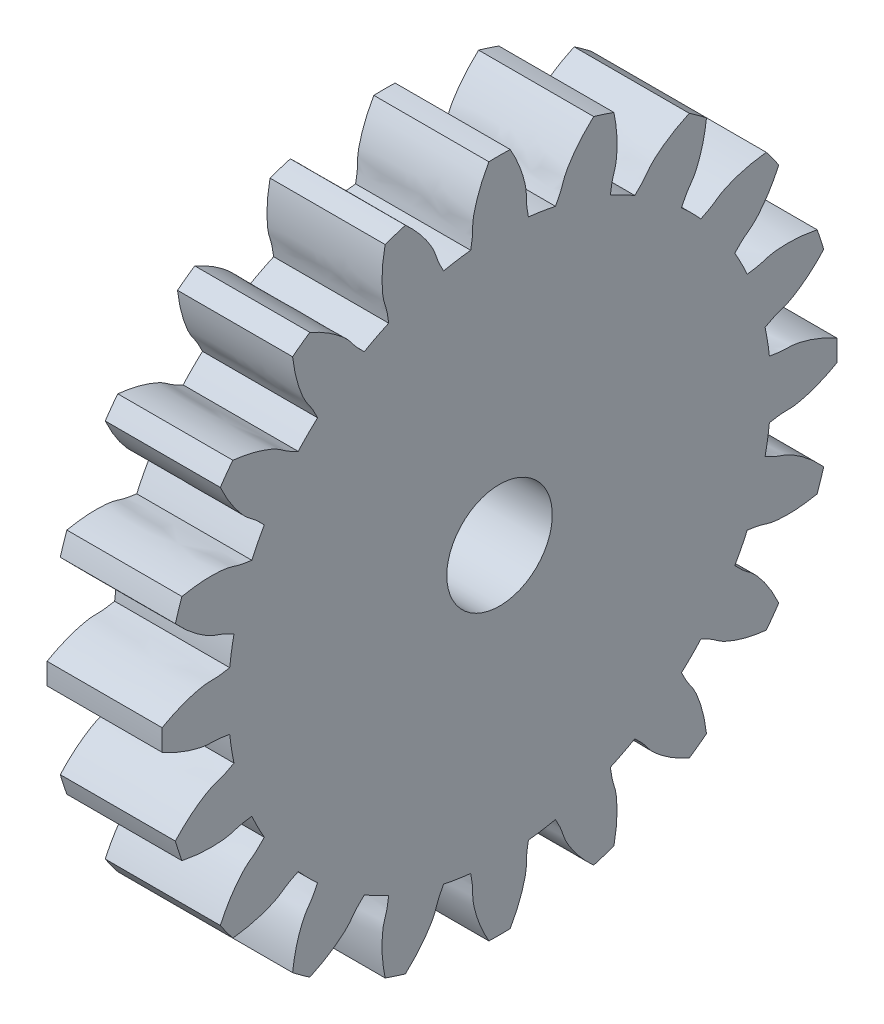
SolidWorks part; units mm, degrees
ref_plane "Front Plane" through (0, 0, 0) normal (0, 0, 1) x (1, 0, 0)
ref_plane "Top Plane" through (0, 0, 0) normal (0, 1, 0) x (1, 0, 0)
ref_plane "Right Plane" through (0, 0, 0) normal (1, 0, 0) x (0, 0, -1)
ref_plane "Plane1" through (0, 2.008, 0) normal (0, -1, 0) x (-1, 0, 0)
ref_plane "Plane2" through (0, 4.8333, 0) normal (0, 1, 0) x (1, 0, 0)
sketch "Sketch41" plane through (0, 0, 0) normal (0, 0, 1) x (1, 0, 0)
  line L0 (-1.5, 8.8) -> (-1.5, 0)
  line L1 (-1.5, 0) -> (1.5, 0)
  line L2 (1.5, 0) -> (1.5, 8.8)
  line L3 (1.5, 8.8) -> (-1.5, 8.8)
  line L4 (-1.5, 0) -> (1.5, 0) construction
revolve "Revolve3" add sketch "Sketch41" angle 360 about L1 reverse direction yes
ref_plane "Plane3" through (-1.5, 0, 0) normal (-1, 0, 0) x (0, 0, 1)
sketch "Sketch47" plane through (-1.5, 0, 0) normal (-1, 0, 0) x (0, 0, 1)
  arc A0 (0.7524, 7.0343) -> (1.4582, 6.9225) centre (0, 0) cw
  arc A1 (2.4537, 8.451) -> (0.2779, 8.7956) centre (0, 0) ccw
  spline S0 degree 3 poles (0.2779, 8.7956) (0.3159, 8.7284) (0.3523, 8.6603) (0.3868, 8.5913) (0.4678, 8.4292) (0.5382, 8.261) (0.5931, 8.0882) (0.6482, 7.9149) (0.6968, 7.7352) (0.7008, 7.5535) (0.7028, 7.4585) (0.7002, 7.3628) (0.7143, 7.2689) (0.7261, 7.1905) (0.7397, 7.1125) (0.7524, 7.0343) knots -0.000231 -0.000231 -0.000231 -0.000231 0 0 0 0.000544 0.000544 0.000544 0.001091 0.001091 0.001091 0.001372 0.001372 0.001372 0.001605 0.001605 0.001605 0.001605
  spline S1 degree 3 poles (1.4582, 6.9225) (1.4944, 6.9929) (1.5314, 7.063) (1.5669, 7.1338) (1.6364, 7.2729) (1.6675, 7.4295) (1.7404, 7.5668) (1.8106, 7.6992) (1.8949, 7.8242) (1.9854, 7.9436) (2.0779, 8.0657) (2.1795, 8.1812) (2.287, 8.2903) (2.3412, 8.3453) (2.3968, 8.3988) (2.4537, 8.451) knots -0.000237 -0.000237 -0.000237 -0.000237 0 0 0 0.000466 0.000466 0.000466 0.000915 0.000915 0.000915 0.001374 0.001374 0.001374 0.001605 0.001605 0.001605 0.001605
extrude "Cut-Extrude22" cut sketch "Sketch47" against normal through all
sketch "Sketch54" plane through (-1.5, 0, 0) normal (-1, 0, 0) x (0, 0, 1)
  arc A0 (2.8893, 6.4575) -> (3.526, 6.1331) centre (0, 0) cw
  arc A1 (4.9451, 7.2791) -> (2.9823, 8.2792) centre (0, 0) ccw
  spline S0 degree 3 poles (2.9823, 8.2792) (2.9976, 8.2036) (3.0112, 8.1276) (3.0227, 8.0513) (3.0497, 7.8721) (3.0646, 7.6903) (3.0635, 7.5091) (3.0623, 7.3272) (3.053, 7.1413) (3.0006, 6.9672) (2.9733, 6.8763) (2.9411, 6.7861) (2.9255, 6.6924) (2.9125, 6.6142) (2.9013, 6.5358) (2.8893, 6.4575) knots -0.000231 -0.000231 -0.000231 -0.000231 0 0 0 0.000544 0.000544 0.000544 0.001091 0.001091 0.001091 0.001372 0.001372 0.001372 0.001605 0.001605 0.001605 0.001605
  spline S1 degree 3 poles (3.526, 6.1331) (3.5822, 6.1889) (3.6391, 6.244) (3.6946, 6.3005) (3.8037, 6.4113) (3.8817, 6.5506) (3.9935, 6.6587) (4.1011, 6.7629) (4.22, 6.8557) (4.3429, 6.9413) (4.4686, 7.0288) (4.601, 7.1073) (4.7369, 7.1779) (4.8054, 7.2134) (4.8749, 7.2471) (4.9451, 7.2791) knots -0.000237 -0.000237 -0.000237 -0.000237 0 0 0 0.000466 0.000466 0.000466 0.000915 0.000915 0.000915 0.001374 0.001374 0.001374 0.001605 0.001605 0.001605 0.001605
extrude "Cut-Extrude23" cut sketch "Sketch54" against normal through all
sketch "Sketch61" plane through (-1.5, 0, 0) normal (-1, 0, 0) x (0, 0, 1)
  arc A0 (4.7433, 5.2486) -> (5.2486, 4.7433) centre (0, 0) cw
  arc A1 (6.9524, 5.3948) -> (5.3948, 6.9524) centre (0, 0) ccw
  spline S0 degree 3 poles (5.3948, 6.9524) (5.386, 6.8758) (5.3754, 6.7993) (5.3628, 6.7232) (5.3331, 6.5444) (5.2911, 6.3669) (5.234, 6.1949) (5.1767, 6.0223) (5.1104, 5.8484) (5.0068, 5.699) (4.9526, 5.6209) (4.8942, 5.5451) (4.8504, 5.4608) (4.8139, 5.3905) (4.779, 5.3194) (4.7433, 5.2486) knots -0.000231 -0.000231 -0.000231 -0.000231 0 0 0 0.000544 0.000544 0.000544 0.001091 0.001091 0.001091 0.001372 0.001372 0.001372 0.001605 0.001605 0.001605 0.001605
  spline S1 degree 3 poles (5.2486, 4.7433) (5.3194, 4.779) (5.3905, 4.8139) (5.4608, 4.8504) (5.5988, 4.9221) (5.716, 5.0305) (5.8557, 5.0987) (5.9903, 5.1645) (6.132, 5.2161) (6.2754, 5.2595) (6.422, 5.304) (6.572, 5.3376) (6.7232, 5.3628) (6.7993, 5.3754) (6.8758, 5.386) (6.9524, 5.3948) knots -0.000237 -0.000237 -0.000237 -0.000237 0 0 0 0.000466 0.000466 0.000466 0.000915 0.000915 0.000915 0.001374 0.001374 0.001374 0.001605 0.001605 0.001605 0.001605
extrude "Cut-Extrude24" cut sketch "Sketch61" against normal through all
sketch "Sketch68" plane through (-1.5, 0, 0) normal (-1, 0, 0) x (0, 0, 1)
  arc A0 (6.1331, 3.526) -> (6.4575, 2.8893) centre (0, 0) cw
  arc A1 (8.2792, 2.9823) -> (7.2791, 4.9451) centre (0, 0) ccw
  spline S0 degree 3 poles (7.2791, 4.9451) (7.2471, 4.8749) (7.2134, 4.8054) (7.1779, 4.7369) (7.0944, 4.5761) (6.9996, 4.4202) (6.8921, 4.2743) (6.7843, 4.1279) (6.6675, 3.9829) (6.5228, 3.8729) (6.4472, 3.8154) (6.3682, 3.7613) (6.3005, 3.6946) (6.244, 3.6391) (6.1889, 3.5822) (6.1331, 3.526) knots -0.000231 -0.000231 -0.000231 -0.000231 0 0 0 0.000544 0.000544 0.000544 0.001091 0.001091 0.001091 0.001372 0.001372 0.001372 0.001605 0.001605 0.001605 0.001605
  spline S1 degree 3 poles (6.4575, 2.8893) (6.5358, 2.9013) (6.6142, 2.9125) (6.6924, 2.9255) (6.8457, 2.9511) (6.9907, 3.0179) (7.1447, 3.0397) (7.293, 3.0607) (7.4437, 3.0659) (7.5935, 3.0629) (7.7466, 3.0599) (7.8998, 3.0455) (8.0513, 3.0227) (8.1276, 3.0112) (8.2036, 2.9976) (8.2792, 2.9823) knots -0.000237 -0.000237 -0.000237 -0.000237 0 0 0 0.000466 0.000466 0.000466 0.000915 0.000915 0.000915 0.001374 0.001374 0.001374 0.001605 0.001605 0.001605 0.001605
extrude "Cut-Extrude25" cut sketch "Sketch68" against normal through all
sketch "Sketch75" plane through (-1.5, 0, 0) normal (-1, 0, 0) x (0, 0, 1)
  arc A0 (6.9225, 1.4582) -> (7.0343, 0.7524) centre (0, 0) cw
  arc A1 (8.7956, 0.2779) -> (8.451, 2.4537) centre (0, 0) ccw
  spline S0 degree 3 poles (8.451, 2.4537) (8.3988, 2.3968) (8.3453, 2.3412) (8.2903, 2.287) (8.1612, 2.1598) (8.0229, 2.0409) (7.8756, 1.9353) (7.7279, 1.8294) (7.572, 1.7276) (7.4003, 1.6677) (7.3107, 1.6364) (7.2188, 1.6093) (7.1338, 1.5669) (7.063, 1.5314) (6.9929, 1.4944) (6.9225, 1.4582) knots -0.000231 -0.000231 -0.000231 -0.000231 0 0 0 0.000544 0.000544 0.000544 0.001091 0.001091 0.001091 0.001372 0.001372 0.001372 0.001605 0.001605 0.001605 0.001605
  spline S1 degree 3 poles (7.0343, 0.7524) (7.1125, 0.7397) (7.1905, 0.7261) (7.2689, 0.7143) (7.4226, 0.6912) (7.5811, 0.71) (7.7343, 0.6831) (7.8819, 0.6572) (8.0268, 0.6156) (8.1683, 0.5665) (8.3131, 0.5163) (8.4543, 0.4553) (8.5913, 0.3868) (8.6603, 0.3523) (8.7284, 0.3159) (8.7956, 0.2779) knots -0.000237 -0.000237 -0.000237 -0.000237 0 0 0 0.000466 0.000466 0.000466 0.000915 0.000915 0.000915 0.001374 0.001374 0.001374 0.001605 0.001605 0.001605 0.001605
extrude "Cut-Extrude26" cut sketch "Sketch75" against normal through all
sketch "Sketch82" plane through (-1.5, 0, 0) normal (-1, 0, 0) x (0, 0, 1)
  arc A0 (8.451, -2.4537) -> (8.7956, -0.2779) centre (0, 0) ccw
  arc A1 (7.0343, -0.7524) -> (6.9225, -1.4582) centre (0, 0) cw
  spline S0 degree 3 poles (8.7956, -0.2779) (8.7284, -0.3159) (8.6603, -0.3523) (8.5913, -0.3868) (8.4292, -0.4678) (8.261, -0.5382) (8.0882, -0.5931) (7.9149, -0.6482) (7.7352, -0.6968) (7.5535, -0.7008) (7.4585, -0.7028) (7.3628, -0.7002) (7.2689, -0.7143) (7.1905, -0.7261) (7.1125, -0.7397) (7.0343, -0.7524) knots -0.000231 -0.000231 -0.000231 -0.000231 0 0 0 0.000544 0.000544 0.000544 0.001091 0.001091 0.001091 0.001372 0.001372 0.001372 0.001605 0.001605 0.001605 0.001605
  spline S1 degree 3 poles (6.9225, -1.4582) (6.9929, -1.4944) (7.063, -1.5314) (7.1338, -1.5669) (7.2729, -1.6364) (7.4295, -1.6675) (7.5668, -1.7404) (7.6992, -1.8106) (7.8242, -1.8949) (7.9436, -1.9854) (8.0657, -2.0779) (8.1812, -2.1795) (8.2903, -2.287) (8.3453, -2.3412) (8.3988, -2.3968) (8.451, -2.4537) knots -0.000237 -0.000237 -0.000237 -0.000237 0 0 0 0.000466 0.000466 0.000466 0.000915 0.000915 0.000915 0.001374 0.001374 0.001374 0.001605 0.001605 0.001605 0.001605
extrude "Cut-Extrude27" cut sketch "Sketch82" against normal through all
sketch "Sketch89" plane through (-1.5, 0, 0) normal (-1, 0, 0) x (0, 0, 1)
  arc A0 (7.2791, -4.9451) -> (8.2792, -2.9823) centre (0, 0) ccw
  arc A1 (6.4575, -2.8893) -> (6.1331, -3.526) centre (0, 0) cw
  spline S0 degree 3 poles (8.2792, -2.9823) (8.2036, -2.9976) (8.1276, -3.0112) (8.0513, -3.0227) (7.8721, -3.0497) (7.6903, -3.0646) (7.5091, -3.0635) (7.3272, -3.0623) (7.1413, -3.053) (6.9672, -3.0006) (6.8763, -2.9733) (6.7861, -2.9411) (6.6924, -2.9255) (6.6142, -2.9125) (6.5358, -2.9013) (6.4575, -2.8893) knots -0.000231 -0.000231 -0.000231 -0.000231 0 0 0 0.000544 0.000544 0.000544 0.001091 0.001091 0.001091 0.001372 0.001372 0.001372 0.001605 0.001605 0.001605 0.001605
  spline S1 degree 3 poles (6.1331, -3.526) (6.1889, -3.5822) (6.244, -3.6391) (6.3005, -3.6946) (6.4113, -3.8037) (6.5506, -3.8817) (6.6587, -3.9935) (6.7629, -4.1011) (6.8557, -4.22) (6.9413, -4.3429) (7.0288, -4.4686) (7.1073, -4.601) (7.1779, -4.7369) (7.2134, -4.8054) (7.2471, -4.8749) (7.2791, -4.9451) knots -0.000237 -0.000237 -0.000237 -0.000237 0 0 0 0.000466 0.000466 0.000466 0.000915 0.000915 0.000915 0.001374 0.001374 0.001374 0.001605 0.001605 0.001605 0.001605
extrude "Cut-Extrude28" cut sketch "Sketch89" against normal through all
sketch "Sketch96" plane through (-1.5, 0, 0) normal (-1, 0, 0) x (0, 0, 1)
  arc A0 (5.3948, -6.9524) -> (6.9524, -5.3948) centre (0, 0) ccw
  arc A1 (5.2486, -4.7433) -> (4.7433, -5.2486) centre (0, 0) cw
  spline S0 degree 3 poles (6.9524, -5.3948) (6.8758, -5.386) (6.7993, -5.3754) (6.7232, -5.3628) (6.5444, -5.3331) (6.3669, -5.2911) (6.1949, -5.234) (6.0223, -5.1767) (5.8484, -5.1104) (5.699, -5.0068) (5.6209, -4.9526) (5.5451, -4.8942) (5.4608, -4.8504) (5.3905, -4.8139) (5.3194, -4.779) (5.2486, -4.7433) knots -0.000231 -0.000231 -0.000231 -0.000231 0 0 0 0.000544 0.000544 0.000544 0.001091 0.001091 0.001091 0.001372 0.001372 0.001372 0.001605 0.001605 0.001605 0.001605
  spline S1 degree 3 poles (4.7433, -5.2486) (4.779, -5.3194) (4.8139, -5.3905) (4.8504, -5.4608) (4.9221, -5.5988) (5.0305, -5.716) (5.0987, -5.8557) (5.1645, -5.9903) (5.2161, -6.132) (5.2595, -6.2754) (5.304, -6.422) (5.3376, -6.572) (5.3628, -6.7232) (5.3754, -6.7993) (5.386, -6.8758) (5.3948, -6.9524) knots -0.000237 -0.000237 -0.000237 -0.000237 0 0 0 0.000466 0.000466 0.000466 0.000915 0.000915 0.000915 0.001374 0.001374 0.001374 0.001605 0.001605 0.001605 0.001605
extrude "Cut-Extrude29" cut sketch "Sketch96" against normal through all
sketch "Sketch103" plane through (-1.5, 0, 0) normal (-1, 0, 0) x (0, 0, 1)
  arc A0 (2.9823, -8.2792) -> (4.9451, -7.2791) centre (0, 0) ccw
  arc A1 (3.526, -6.1331) -> (2.8893, -6.4575) centre (0, 0) cw
  spline S0 degree 3 poles (4.9451, -7.2791) (4.8749, -7.2471) (4.8054, -7.2134) (4.7369, -7.1779) (4.5761, -7.0944) (4.4202, -6.9996) (4.2743, -6.8921) (4.1279, -6.7843) (3.9829, -6.6675) (3.8729, -6.5228) (3.8154, -6.4472) (3.7613, -6.3682) (3.6946, -6.3005) (3.6391, -6.244) (3.5822, -6.1889) (3.526, -6.1331) knots -0.000231 -0.000231 -0.000231 -0.000231 0 0 0 0.000544 0.000544 0.000544 0.001091 0.001091 0.001091 0.001372 0.001372 0.001372 0.001605 0.001605 0.001605 0.001605
  spline S1 degree 3 poles (2.8893, -6.4575) (2.9013, -6.5358) (2.9125, -6.6142) (2.9255, -6.6924) (2.9511, -6.8457) (3.0179, -6.9907) (3.0397, -7.1447) (3.0607, -7.293) (3.0659, -7.4437) (3.0629, -7.5935) (3.0599, -7.7466) (3.0455, -7.8998) (3.0227, -8.0513) (3.0112, -8.1276) (2.9976, -8.2036) (2.9823, -8.2792) knots -0.000237 -0.000237 -0.000237 -0.000237 0 0 0 0.000466 0.000466 0.000466 0.000915 0.000915 0.000915 0.001374 0.001374 0.001374 0.001605 0.001605 0.001605 0.001605
extrude "Cut-Extrude30" cut sketch "Sketch103" against normal through all
sketch "Sketch110" plane through (-1.5, 0, 0) normal (-1, 0, 0) x (0, 0, 1)
  arc A0 (0.2779, -8.7956) -> (2.4537, -8.451) centre (0, 0) ccw
  arc A1 (1.4582, -6.9225) -> (0.7524, -7.0343) centre (0, 0) cw
  spline S0 degree 3 poles (2.4537, -8.451) (2.3968, -8.3988) (2.3412, -8.3453) (2.287, -8.2903) (2.1598, -8.1612) (2.0409, -8.0229) (1.9353, -7.8756) (1.8294, -7.7279) (1.7276, -7.572) (1.6677, -7.4003) (1.6364, -7.3107) (1.6093, -7.2188) (1.5669, -7.1338) (1.5314, -7.063) (1.4944, -6.9929) (1.4582, -6.9225) knots -0.000231 -0.000231 -0.000231 -0.000231 0 0 0 0.000544 0.000544 0.000544 0.001091 0.001091 0.001091 0.001372 0.001372 0.001372 0.001605 0.001605 0.001605 0.001605
  spline S1 degree 3 poles (0.7524, -7.0343) (0.7397, -7.1125) (0.7261, -7.1905) (0.7143, -7.2689) (0.6912, -7.4226) (0.71, -7.5811) (0.6831, -7.7343) (0.6572, -7.8819) (0.6156, -8.0268) (0.5665, -8.1683) (0.5163, -8.3131) (0.4553, -8.4543) (0.3868, -8.5913) (0.3523, -8.6603) (0.3159, -8.7284) (0.2779, -8.7956) knots -0.000237 -0.000237 -0.000237 -0.000237 0 0 0 0.000466 0.000466 0.000466 0.000915 0.000915 0.000915 0.001374 0.001374 0.001374 0.001605 0.001605 0.001605 0.001605
extrude "Cut-Extrude31" cut sketch "Sketch110" against normal through all
sketch "Sketch117" plane through (-1.5, 0, 0) normal (-1, 0, 0) x (0, 0, 1)
  arc A0 (-0.7524, -7.0343) -> (-1.4582, -6.9225) centre (0, 0) cw
  arc A1 (-2.4537, -8.451) -> (-0.2779, -8.7956) centre (0, 0) ccw
  spline S0 degree 3 poles (-0.2779, -8.7956) (-0.3159, -8.7284) (-0.3523, -8.6603) (-0.3868, -8.5913) (-0.4678, -8.4292) (-0.5382, -8.261) (-0.5931, -8.0882) (-0.6482, -7.9149) (-0.6968, -7.7352) (-0.7008, -7.5535) (-0.7028, -7.4585) (-0.7002, -7.3628) (-0.7143, -7.2689) (-0.7261, -7.1905) (-0.7397, -7.1125) (-0.7524, -7.0343) knots -0.000231 -0.000231 -0.000231 -0.000231 0 0 0 0.000544 0.000544 0.000544 0.001091 0.001091 0.001091 0.001372 0.001372 0.001372 0.001605 0.001605 0.001605 0.001605
  spline S1 degree 3 poles (-1.4582, -6.9225) (-1.4944, -6.9929) (-1.5314, -7.063) (-1.5669, -7.1338) (-1.6364, -7.2729) (-1.6675, -7.4295) (-1.7404, -7.5668) (-1.8106, -7.6992) (-1.8949, -7.8242) (-1.9854, -7.9436) (-2.0779, -8.0657) (-2.1795, -8.1812) (-2.287, -8.2903) (-2.3412, -8.3453) (-2.3968, -8.3988) (-2.4537, -8.451) knots -0.000237 -0.000237 -0.000237 -0.000237 0 0 0 0.000466 0.000466 0.000466 0.000915 0.000915 0.000915 0.001374 0.001374 0.001374 0.001605 0.001605 0.001605 0.001605
extrude "Cut-Extrude32" cut sketch "Sketch117" against normal through all
sketch "Sketch124" plane through (-1.5, 0, 0) normal (-1, 0, 0) x (0, 0, 1)
  arc A0 (-2.8893, -6.4575) -> (-3.526, -6.1331) centre (0, 0) cw
  arc A1 (-4.9451, -7.2791) -> (-2.9823, -8.2792) centre (0, 0) ccw
  spline S0 degree 3 poles (-2.9823, -8.2792) (-2.9976, -8.2036) (-3.0112, -8.1276) (-3.0227, -8.0513) (-3.0497, -7.8721) (-3.0646, -7.6903) (-3.0635, -7.5091) (-3.0623, -7.3272) (-3.053, -7.1413) (-3.0006, -6.9672) (-2.9733, -6.8763) (-2.9411, -6.7861) (-2.9255, -6.6924) (-2.9125, -6.6142) (-2.9013, -6.5358) (-2.8893, -6.4575) knots -0.000231 -0.000231 -0.000231 -0.000231 0 0 0 0.000544 0.000544 0.000544 0.001091 0.001091 0.001091 0.001372 0.001372 0.001372 0.001605 0.001605 0.001605 0.001605
  spline S1 degree 3 poles (-3.526, -6.1331) (-3.5822, -6.1889) (-3.6391, -6.244) (-3.6946, -6.3005) (-3.8037, -6.4113) (-3.8817, -6.5506) (-3.9935, -6.6587) (-4.1011, -6.7629) (-4.22, -6.8557) (-4.3429, -6.9413) (-4.4686, -7.0288) (-4.601, -7.1073) (-4.7369, -7.1779) (-4.8054, -7.2134) (-4.8749, -7.2471) (-4.9451, -7.2791) knots -0.000237 -0.000237 -0.000237 -0.000237 0 0 0 0.000466 0.000466 0.000466 0.000915 0.000915 0.000915 0.001374 0.001374 0.001374 0.001605 0.001605 0.001605 0.001605
extrude "Cut-Extrude33" cut sketch "Sketch124" against normal through all
sketch "Sketch131" plane through (-1.5, 0, 0) normal (-1, 0, 0) x (0, 0, 1)
  arc A0 (-6.9524, -5.3948) -> (-5.3948, -6.9524) centre (0, 0) ccw
  arc A1 (-4.7433, -5.2486) -> (-5.2486, -4.7433) centre (0, 0) cw
  spline S0 degree 3 poles (-5.3948, -6.9524) (-5.386, -6.8758) (-5.3754, -6.7993) (-5.3628, -6.7232) (-5.3331, -6.5444) (-5.2911, -6.3669) (-5.234, -6.1949) (-5.1767, -6.0223) (-5.1104, -5.8484) (-5.0068, -5.699) (-4.9526, -5.6209) (-4.8942, -5.5451) (-4.8504, -5.4608) (-4.8139, -5.3905) (-4.779, -5.3194) (-4.7433, -5.2486) knots -0.000231 -0.000231 -0.000231 -0.000231 0 0 0 0.000544 0.000544 0.000544 0.001091 0.001091 0.001091 0.001372 0.001372 0.001372 0.001605 0.001605 0.001605 0.001605
  spline S1 degree 3 poles (-5.2486, -4.7433) (-5.3194, -4.779) (-5.3905, -4.8139) (-5.4608, -4.8504) (-5.5988, -4.9221) (-5.716, -5.0305) (-5.8557, -5.0987) (-5.9903, -5.1645) (-6.132, -5.2161) (-6.2754, -5.2595) (-6.422, -5.304) (-6.572, -5.3376) (-6.7232, -5.3628) (-6.7993, -5.3754) (-6.8758, -5.386) (-6.9524, -5.3948) knots -0.000237 -0.000237 -0.000237 -0.000237 0 0 0 0.000466 0.000466 0.000466 0.000915 0.000915 0.000915 0.001374 0.001374 0.001374 0.001605 0.001605 0.001605 0.001605
extrude "Cut-Extrude34" cut sketch "Sketch131" against normal through all
sketch "Sketch138" plane through (-1.5, 0, 0) normal (-1, 0, 0) x (0, 0, 1)
  arc A0 (-8.2792, -2.9823) -> (-7.2791, -4.9451) centre (0, 0) ccw
  arc A1 (-6.1331, -3.526) -> (-6.4575, -2.8893) centre (0, 0) cw
  spline S0 degree 3 poles (-7.2791, -4.9451) (-7.2471, -4.8749) (-7.2134, -4.8054) (-7.1779, -4.7369) (-7.0944, -4.5761) (-6.9996, -4.4202) (-6.8921, -4.2743) (-6.7843, -4.1279) (-6.6675, -3.9829) (-6.5228, -3.8729) (-6.4472, -3.8154) (-6.3682, -3.7613) (-6.3005, -3.6946) (-6.244, -3.6391) (-6.1889, -3.5822) (-6.1331, -3.526) knots -0.000231 -0.000231 -0.000231 -0.000231 0 0 0 0.000544 0.000544 0.000544 0.001091 0.001091 0.001091 0.001372 0.001372 0.001372 0.001605 0.001605 0.001605 0.001605
  spline S1 degree 3 poles (-6.4575, -2.8893) (-6.5358, -2.9013) (-6.6142, -2.9125) (-6.6924, -2.9255) (-6.8457, -2.9511) (-6.9907, -3.0179) (-7.1447, -3.0397) (-7.293, -3.0607) (-7.4437, -3.0659) (-7.5935, -3.0629) (-7.7466, -3.0599) (-7.8998, -3.0455) (-8.0513, -3.0227) (-8.1276, -3.0112) (-8.2036, -2.9976) (-8.2792, -2.9823) knots -0.000237 -0.000237 -0.000237 -0.000237 0 0 0 0.000466 0.000466 0.000466 0.000915 0.000915 0.000915 0.001374 0.001374 0.001374 0.001605 0.001605 0.001605 0.001605
extrude "Cut-Extrude35" cut sketch "Sketch138" against normal through all
sketch "Sketch145" plane through (-1.5, 0, 0) normal (-1, 0, 0) x (0, 0, 1)
  arc A0 (-8.7956, -0.2779) -> (-8.451, -2.4537) centre (0, 0) ccw
  arc A1 (-6.9225, -1.4582) -> (-7.0343, -0.7524) centre (0, 0) cw
  spline S0 degree 3 poles (-8.451, -2.4537) (-8.3988, -2.3968) (-8.3453, -2.3412) (-8.2903, -2.287) (-8.1612, -2.1598) (-8.0229, -2.0409) (-7.8756, -1.9353) (-7.7279, -1.8294) (-7.572, -1.7276) (-7.4003, -1.6677) (-7.3107, -1.6364) (-7.2188, -1.6093) (-7.1338, -1.5669) (-7.063, -1.5314) (-6.9929, -1.4944) (-6.9225, -1.4582) knots -0.000231 -0.000231 -0.000231 -0.000231 0 0 0 0.000544 0.000544 0.000544 0.001091 0.001091 0.001091 0.001372 0.001372 0.001372 0.001605 0.001605 0.001605 0.001605
  spline S1 degree 3 poles (-7.0343, -0.7524) (-7.1125, -0.7397) (-7.1905, -0.7261) (-7.2689, -0.7143) (-7.4226, -0.6912) (-7.5811, -0.71) (-7.7343, -0.6831) (-7.8819, -0.6572) (-8.0268, -0.6156) (-8.1683, -0.5665) (-8.3131, -0.5163) (-8.4543, -0.4553) (-8.5913, -0.3868) (-8.6603, -0.3523) (-8.7284, -0.3159) (-8.7956, -0.2779) knots -0.000237 -0.000237 -0.000237 -0.000237 0 0 0 0.000466 0.000466 0.000466 0.000915 0.000915 0.000915 0.001374 0.001374 0.001374 0.001605 0.001605 0.001605 0.001605
extrude "Cut-Extrude36" cut sketch "Sketch145" against normal through all
sketch "Sketch152" plane through (-1.5, 0, 0) normal (-1, 0, 0) x (0, 0, 1)
  arc A0 (-8.451, 2.4537) -> (-8.7956, 0.2779) centre (0, 0) ccw
  arc A1 (-7.0343, 0.7524) -> (-6.9225, 1.4582) centre (0, 0) cw
  spline S0 degree 3 poles (-8.7956, 0.2779) (-8.7284, 0.3159) (-8.6603, 0.3523) (-8.5913, 0.3868) (-8.4292, 0.4678) (-8.261, 0.5382) (-8.0882, 0.5931) (-7.9149, 0.6482) (-7.7352, 0.6968) (-7.5535, 0.7008) (-7.4585, 0.7028) (-7.3628, 0.7002) (-7.2689, 0.7143) (-7.1905, 0.7261) (-7.1125, 0.7397) (-7.0343, 0.7524) knots -0.000231 -0.000231 -0.000231 -0.000231 0 0 0 0.000544 0.000544 0.000544 0.001091 0.001091 0.001091 0.001372 0.001372 0.001372 0.001605 0.001605 0.001605 0.001605
  spline S1 degree 3 poles (-6.9225, 1.4582) (-6.9929, 1.4944) (-7.063, 1.5314) (-7.1338, 1.5669) (-7.2729, 1.6364) (-7.4295, 1.6675) (-7.5668, 1.7404) (-7.6992, 1.8106) (-7.8242, 1.8949) (-7.9436, 1.9854) (-8.0657, 2.0779) (-8.1812, 2.1795) (-8.2903, 2.287) (-8.3453, 2.3412) (-8.3988, 2.3968) (-8.451, 2.4537) knots -0.000237 -0.000237 -0.000237 -0.000237 0 0 0 0.000466 0.000466 0.000466 0.000915 0.000915 0.000915 0.001374 0.001374 0.001374 0.001605 0.001605 0.001605 0.001605
extrude "Cut-Extrude37" cut sketch "Sketch152" against normal through all
sketch "Sketch159" plane through (-1.5, 0, 0) normal (-1, 0, 0) x (0, 0, 1)
  arc A0 (-7.2791, 4.9451) -> (-8.2792, 2.9823) centre (0, 0) ccw
  arc A1 (-6.4575, 2.8893) -> (-6.1331, 3.526) centre (0, 0) cw
  spline S0 degree 3 poles (-8.2792, 2.9823) (-8.2036, 2.9976) (-8.1276, 3.0112) (-8.0513, 3.0227) (-7.8721, 3.0497) (-7.6903, 3.0646) (-7.5091, 3.0635) (-7.3272, 3.0623) (-7.1413, 3.053) (-6.9672, 3.0006) (-6.8763, 2.9733) (-6.7861, 2.9411) (-6.6924, 2.9255) (-6.6142, 2.9125) (-6.5358, 2.9013) (-6.4575, 2.8893) knots -0.000231 -0.000231 -0.000231 -0.000231 0 0 0 0.000544 0.000544 0.000544 0.001091 0.001091 0.001091 0.001372 0.001372 0.001372 0.001605 0.001605 0.001605 0.001605
  spline S1 degree 3 poles (-6.1331, 3.526) (-6.1889, 3.5822) (-6.244, 3.6391) (-6.3005, 3.6946) (-6.4113, 3.8037) (-6.5506, 3.8817) (-6.6587, 3.9935) (-6.7629, 4.1011) (-6.8557, 4.22) (-6.9413, 4.3429) (-7.0288, 4.4686) (-7.1073, 4.601) (-7.1779, 4.7369) (-7.2134, 4.8054) (-7.2471, 4.8749) (-7.2791, 4.9451) knots -0.000237 -0.000237 -0.000237 -0.000237 0 0 0 0.000466 0.000466 0.000466 0.000915 0.000915 0.000915 0.001374 0.001374 0.001374 0.001605 0.001605 0.001605 0.001605
extrude "Cut-Extrude38" cut sketch "Sketch159" against normal through all
sketch "Sketch166" plane through (-1.5, 0, 0) normal (-1, 0, 0) x (0, 0, 1)
  arc A0 (-5.3948, 6.9524) -> (-6.9524, 5.3948) centre (0, 0) ccw
  arc A1 (-5.2486, 4.7433) -> (-4.7433, 5.2486) centre (0, 0) cw
  spline S0 degree 3 poles (-6.9524, 5.3948) (-6.8758, 5.386) (-6.7993, 5.3754) (-6.7232, 5.3628) (-6.5444, 5.3331) (-6.3669, 5.2911) (-6.1949, 5.234) (-6.0223, 5.1767) (-5.8484, 5.1104) (-5.699, 5.0068) (-5.6209, 4.9526) (-5.5451, 4.8942) (-5.4608, 4.8504) (-5.3905, 4.8139) (-5.3194, 4.779) (-5.2486, 4.7433) knots -0.000231 -0.000231 -0.000231 -0.000231 0 0 0 0.000544 0.000544 0.000544 0.001091 0.001091 0.001091 0.001372 0.001372 0.001372 0.001605 0.001605 0.001605 0.001605
  spline S1 degree 3 poles (-4.7433, 5.2486) (-4.779, 5.3194) (-4.8139, 5.3905) (-4.8504, 5.4608) (-4.9221, 5.5988) (-5.0305, 5.716) (-5.0987, 5.8557) (-5.1645, 5.9903) (-5.2161, 6.132) (-5.2595, 6.2754) (-5.304, 6.422) (-5.3376, 6.572) (-5.3628, 6.7232) (-5.3754, 6.7993) (-5.386, 6.8758) (-5.3948, 6.9524) knots -0.000237 -0.000237 -0.000237 -0.000237 0 0 0 0.000466 0.000466 0.000466 0.000915 0.000915 0.000915 0.001374 0.001374 0.001374 0.001605 0.001605 0.001605 0.001605
extrude "Cut-Extrude39" cut sketch "Sketch166" against normal through all
sketch "Sketch173" plane through (-1.5, 0, 0) normal (-1, 0, 0) x (0, 0, 1)
  arc A0 (-2.9823, 8.2792) -> (-4.9451, 7.2791) centre (0, 0) ccw
  arc A1 (-3.526, 6.1331) -> (-2.8893, 6.4575) centre (0, 0) cw
  spline S0 degree 3 poles (-4.9451, 7.2791) (-4.8749, 7.2471) (-4.8054, 7.2134) (-4.7369, 7.1779) (-4.5761, 7.0944) (-4.4202, 6.9996) (-4.2743, 6.8921) (-4.1279, 6.7843) (-3.9829, 6.6675) (-3.8729, 6.5228) (-3.8154, 6.4472) (-3.7613, 6.3682) (-3.6946, 6.3005) (-3.6391, 6.244) (-3.5822, 6.1889) (-3.526, 6.1331) knots -0.000231 -0.000231 -0.000231 -0.000231 0 0 0 0.000544 0.000544 0.000544 0.001091 0.001091 0.001091 0.001372 0.001372 0.001372 0.001605 0.001605 0.001605 0.001605
  spline S1 degree 3 poles (-2.8893, 6.4575) (-2.9013, 6.5358) (-2.9125, 6.6142) (-2.9255, 6.6924) (-2.9511, 6.8457) (-3.0179, 6.9907) (-3.0397, 7.1447) (-3.0607, 7.293) (-3.0659, 7.4437) (-3.0629, 7.5935) (-3.0599, 7.7466) (-3.0455, 7.8998) (-3.0227, 8.0513) (-3.0112, 8.1276) (-2.9976, 8.2036) (-2.9823, 8.2792) knots -0.000237 -0.000237 -0.000237 -0.000237 0 0 0 0.000466 0.000466 0.000466 0.000915 0.000915 0.000915 0.001374 0.001374 0.001374 0.001605 0.001605 0.001605 0.001605
extrude "Cut-Extrude40" cut sketch "Sketch173" against normal through all
sketch "Sketch180" plane through (-1.5, 0, 0) normal (-1, 0, 0) x (0, 0, 1)
  arc A0 (-0.2779, 8.7956) -> (-2.4537, 8.451) centre (0, 0) ccw
  arc A1 (-1.4582, 6.9225) -> (-0.7524, 7.0343) centre (0, 0) cw
  spline S0 degree 3 poles (-2.4537, 8.451) (-2.3968, 8.3988) (-2.3412, 8.3453) (-2.287, 8.2903) (-2.1598, 8.1612) (-2.0409, 8.0229) (-1.9353, 7.8756) (-1.8294, 7.7279) (-1.7276, 7.572) (-1.6677, 7.4003) (-1.6364, 7.3107) (-1.6093, 7.2188) (-1.5669, 7.1338) (-1.5314, 7.063) (-1.4944, 6.9929) (-1.4582, 6.9225) knots -0.000231 -0.000231 -0.000231 -0.000231 0 0 0 0.000544 0.000544 0.000544 0.001091 0.001091 0.001091 0.001372 0.001372 0.001372 0.001605 0.001605 0.001605 0.001605
  spline S1 degree 3 poles (-0.7524, 7.0343) (-0.7397, 7.1125) (-0.7261, 7.1905) (-0.7143, 7.2689) (-0.6912, 7.4226) (-0.71, 7.5811) (-0.6831, 7.7343) (-0.6572, 7.8819) (-0.6156, 8.0268) (-0.5665, 8.1683) (-0.5163, 8.3131) (-0.4553, 8.4543) (-0.3868, 8.5913) (-0.3523, 8.6603) (-0.3159, 8.7284) (-0.2779, 8.7956) knots -0.000237 -0.000237 -0.000237 -0.000237 0 0 0 0.000466 0.000466 0.000466 0.000915 0.000915 0.000915 0.001374 0.001374 0.001374 0.001605 0.001605 0.001605 0.001605
extrude "Cut-Extrude41" cut sketch "Sketch180" against normal through all
ref_plane "Plane4" through (1.5, 0, 0) normal (1, 0, 0) x (0, 0, -1)
sketch "Sketch192" plane through (-1.5, 0, 0) normal (-1, 0, 0) x (0, 0, 1)
  circle A0 centre (0, 0) radius 1.375
  dimension "D1" = 2.75
extrude "Cut-Extrude42" cut sketch "Sketch192" against normal through all
